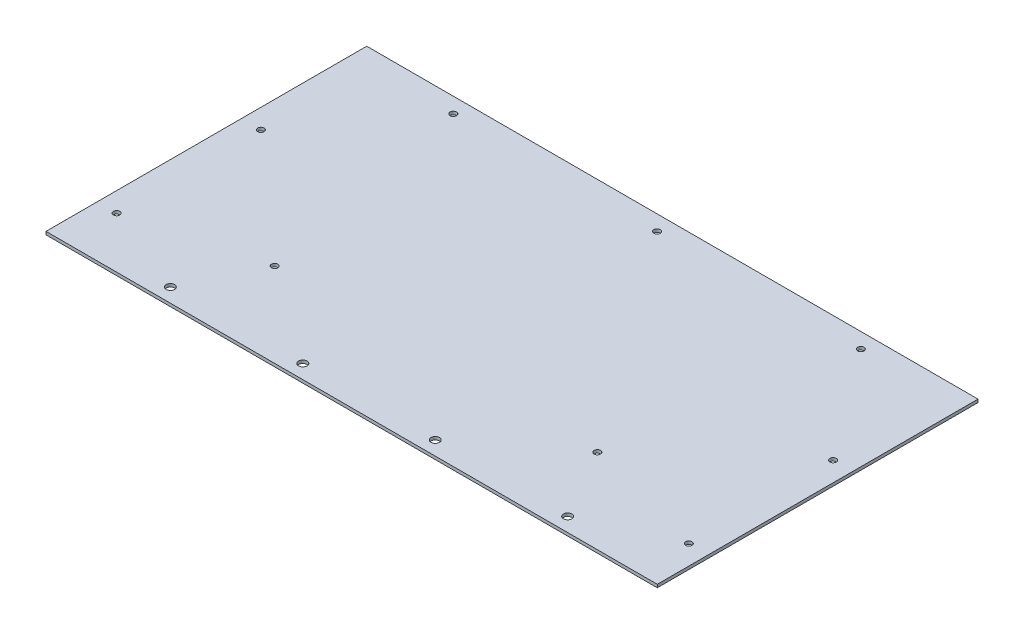
SolidWorks part; units mm, degrees
material "6061-T6 (SS)"
ref_plane "X-Y Datum" through (0, 0, 0) normal (0, 0, 1) x (1, 0, 0)
ref_plane "X-Z Datum" through (0, 0, 0) normal (0, 1, 0) x (1, 0, 0)
ref_plane "Y-Z Datum" through (0, 0, 0) normal (1, 0, 0) x (0, 0, -1)
sketch "Sketch1" plane through (0, 0, 0) normal (0, 0, 1) x (1, 0, 0)
  line L1 (-228.6115, -1.143) -> (228.6115, -1.143)
  line L2 (-228.6115, -1.143) -> (-228.6115, 1.143)
  line L3 (-228.6115, 1.143) -> (228.6115, 1.143)
  line L4 (228.6115, -1.143) -> (228.6115, 1.143)
  line L5 (-228.6115, -1.143) -> (228.6115, 1.143) construction
  line L6 (-228.6115, 1.143) -> (228.6115, -1.143) construction
  point P0 (0, 0)
  dimension "D1" = 2.286
  dimension "D2" = 457.223
extrude "Boss-Extrude1" add sketch "Sketch1" along normal blind 238.3152
sketch "Sketch2" plane through (0, 0, 0) normal (0, 0, -1) x (-1, 0, 0)
  line L22 (-228.6115, 1.143) -> (-228.6115, -1.143)
  line L23 (-228.6115, -1.143) -> (228.6115, -1.143)
  line L24 (228.6115, -1.143) -> (228.6115, 1.143)
  line L25 (228.6115, 1.143) -> (-228.6115, 1.143)
  line L26 (-228.6115, 1.143) -> (-228.6115, -1.143)
  line L27 (-228.6115, -1.143) -> (228.6115, -1.143)
  line L28 (228.6115, -1.143) -> (228.6115, 1.143)
  line L29 (228.6115, 1.143) -> (-228.6115, 1.143)
  dimension "D1" = 0
extrude "Boss-Extrude2" [suppressed] add sketch "Sketch2" along normal blind 3.175
sketch "Sketch9" plane through (0, 1.143, 0) normal (0, 1, 0) x (1, 0, 0)
  line L0 (-146.0615, -238.3152) -> (-146.0615, -229.4252) construction
  line L1 (228.6115, -238.3152) -> (-228.6115, -238.3152) construction
  line L2 (-228.6115, -238.3152) -> (-228.6115, 0) construction
  circle A0 centre (-146.0615, -229.4252) radius 3.175
  dimension "D2" = 82.55
  dimension "D3" = 6.35
  dimension "D1" = 8.89
extrude "Cut-Extrude10" cut sketch "Sketch9" against normal blind 2.54
pattern_linear "LPattern1" count 4 spacing 99.06 along (1, 0, 0) of "Cut-Extrude10"
sketch "Sketch10" plane through (0, -1.143, 0) normal (0, -1, 0) x (1, 0, 0)
  circle A0 centre (151.1185, 229.4252) radius 3.175 construction
  circle A1 centre (52.0585, 229.4252) radius 3.175 construction
  circle A2 centre (-47.0015, 229.4252) radius 3.175 construction
  circle A3 centre (-146.0615, 229.4252) radius 3.175 construction
  circle A4 centre (151.1185, 229.4252) radius 3.175
  circle A5 centre (52.0585, 229.4252) radius 3.175
  circle A6 centre (-47.0015, 229.4252) radius 3.175
  circle A7 centre (-146.0615, 229.4252) radius 3.175
sketch "Sketch15" plane through (0, 0, 238.3152) normal (0, 0, 1) x (1, 0, 0)
  line L4 (228.6115, -1.143) -> (228.6115, 1.143)
  line L5 (228.6115, 1.143) -> (-228.6115, 1.143)
  line L6 (-228.6115, 1.143) -> (-228.6115, -1.143)
  line L7 (-228.6115, -1.143) -> (228.6115, -1.143)
  line L8 (228.6115, -1.143) -> (228.6115, 1.143)
  line L9 (228.6115, 1.143) -> (-228.6115, 1.143)
  line L10 (-228.6115, 1.143) -> (-228.6115, -1.143)
  line L11 (-228.6115, -1.143) -> (228.6115, -1.143)
  dimension "D1" = 0
extrude "Boss-Extrude3" add sketch "Sketch15" along normal blind 1.5875
sketch "Sketch17" plane through (0, -1.143, 0) normal (0, -1, 0) x (1, 0, 0)
  point P0 (-214.0065, 201.7248)
  point P1 (-214.0065, 93.7748)
  point P3 (-152.4, 11.43)
  point P5 (0, 11.43)
  point P7 (152.4, 11.43)
  point P9 (214.0065, 93.7748)
  point P11 (214.0065, 201.7248)
  point P13 (120.65, 176.776)
  point P15 (-120.65, 176.776)
hole_wizard "M4 Clearance Hole1" positions "Sketch17" profile "Sketch18" hole size "M4" standard "ANSI Metric" end condition through all
sketch "Sketch18" plane through (-214.0065, -1.143, 201.7248) normal (1, 0, 0) x (0, 0, -1)
  line L0 (0, 0) -> (0, 2.286)
  line L1 (0, 2.286) -> (2.4, 2.286)
  line L2 (2.4, 2.286) -> (2.4, 0)
  line L5 (2.4, 0) -> (0, 0)
  line L11 (0, -6.35) -> (0, 107.95) construction
  dimension "Thru Hole Dia." = 4.8
  dimension "Thru Hole Depth" = 2.286
